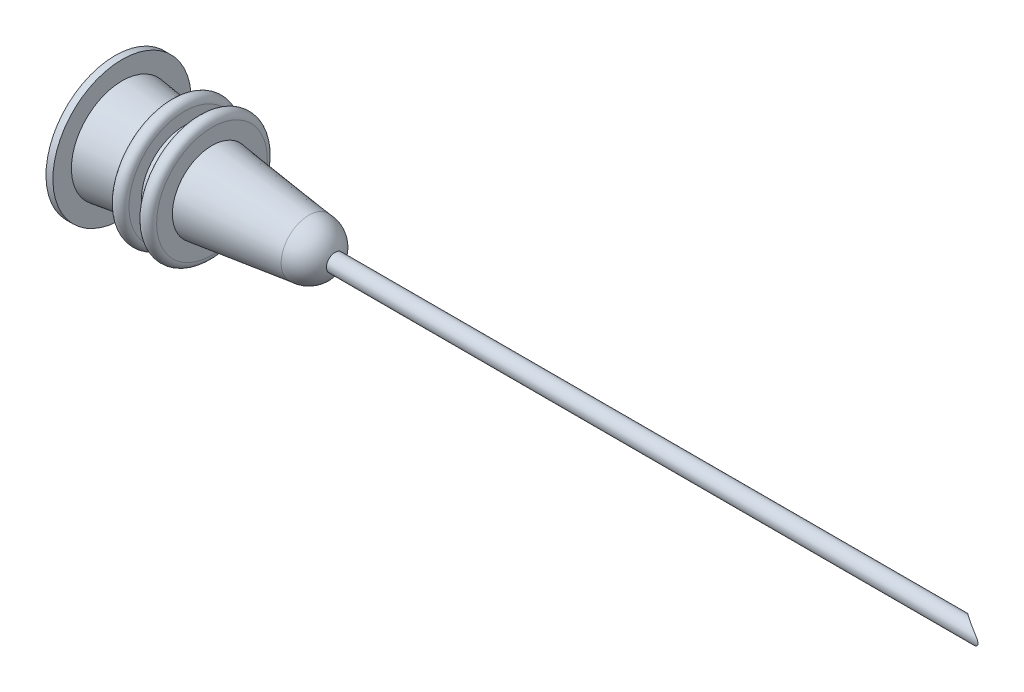
SolidWorks part; units mm, degrees
ref_plane "Plan de face" through (0, 0, 0) normal (0, 0, 1) x (1, 0, 0)
ref_plane "Plan de dessus" through (0, 0, 0) normal (0, 1, 0) x (1, 0, 0)
ref_plane "Plan de droite" through (0, 0, 0) normal (1, 0, 0) x (0, 0, -1)
sketch "Esquisse1" plane through (0, 0, 0) normal (0, 0, 1) x (1, 0, 0)
  line L0 (0, 0) -> (-1, 0)
  line L1 (-1, 0) -> (-1, 1.3674)
  line L2 (-1, 1.3674) -> (-14, 2.9674)
  line L3 (-14, 2.9674) -> (-14, 5)
  line L4 (-14, 5) -> (-13.5, 5)
  line L5 (-13.5, 5) -> (-13.5, 3.6615)
  line L6 (-13.5, 3.6615) -> (-10, 3.2308)
  line L7 (-10, 3.2308) -> (-10, 4)
  line L8 (-9, 4) -> (-9, 3.1077)
  line L9 (-9, 3.1077) -> (-8, 2.9846)
  line L10 (-8, 2.9846) -> (-8, 4)
  line L11 (-7, 4) -> (-7, 2.8615)
  line L13 (-7, 2.8615) -> (0, 2)
  line L14 (0, 2) -> (0, 0)
  line L15 (18.5172, 0) -> (-18.5172, 0) construction
  arc A0 (-10, 4) -> (-9, 4) centre (-9.5, 4) cw
  arc A1 (-8, 4) -> (-7, 4) centre (-7.5, 4) cw
  point P25 (0, 0)
  dimension "D2" = 2
  dimension "D3" = 0.5
  dimension "D8" = 0.5
  dimension "D1" = 1
  dimension "D4" = 7.5
  dimension "D5" = 0.75
  dimension "D6" = 1.6
  dimension "D7" = 2
  dimension "D9" = 14
  dimension "D10" = 0.5
  dimension "D11" = 4
  dimension "D12" = 5
revolve "Révolution1" add sketch "Esquisse1" angle 360 about L15
dome "Dôme1" faces to dome 1 distance 2 reverse direction no elliptical dome no face at (0, 2, 0) parameters "D1"=2
sketch "Esquisse2" plane through (-1, 0, 0) normal (-1, 0, 0) x (0, 0, 1)
  circle A0 centre (0, 0) radius 0.5
  dimension "D1" = 1
extrude "Enlèv. mat.-Extru.1" cut sketch "Esquisse2" against normal blind 10
sketch "Esquisse3" plane through (-1, 0, 0) normal (-1, 0, 0) x (0, 0, 1)
  circle A0 centre (0, 0) radius 0.5
extrude "Extru.-Mince1" add sketch "Esquisse3" against normal blind 50 thin thin type one direction wall 0.125
sketch "Esquisse4" plane through (0, 0, 0) normal (0, 1, 0) x (1, 0, 0)
  line L0 (49, 0.5) -> (49, 3.4275) construction
  line L1 (49, 0) -> (-1, 0) construction
  circle A0 centre (49, 3.5) radius 3.5
  dimension "D1" = 7
extrude "Enlèv. mat.-Extru.2" cut sketch "Esquisse4" against normal mid plane 50
sketch "Esquisse5" plane through (0, 0, 0) normal (0, 1, 0) x (1, 0, 0)
  line L0 (49, -0.625) -> (51, -0.625) construction
  line L1 (51, -0.625) -> (51, 1.3653) construction
  circle A0 centre (50.567, 4.1231) radius 5
  dimension "D2" = 10
  dimension "D1" = 2
extrude "Enlèv. mat.-Extru.3" cut sketch "Esquisse5" against normal mid plane 50
